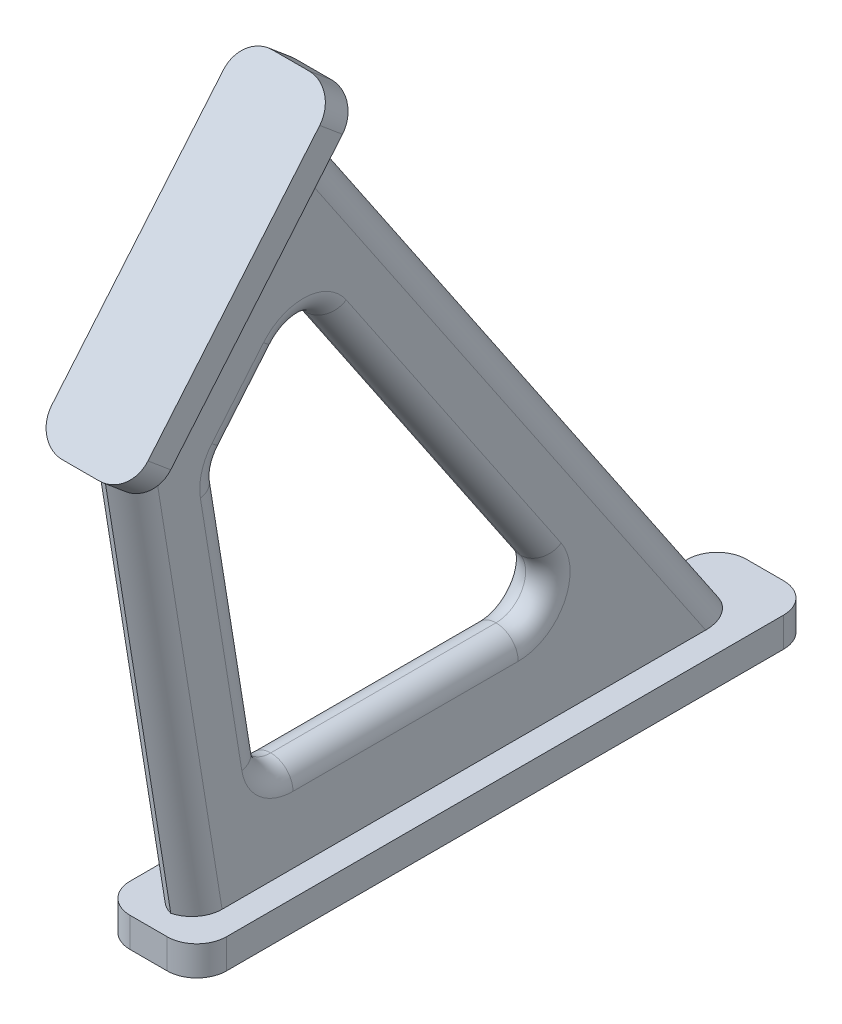
SolidWorks part; units mm, degrees
ref_plane "Front Plane" through (0, 0, 0) normal (0, 0, 1) x (1, 0, 0)
ref_plane "Top Plane" through (0, 0, 0) normal (0, 1, 0) x (1, 0, 0)
ref_plane "Right Plane" through (0, 0, 0) normal (1, 0, 0) x (0, 0, -1)
sketch "Sketch1" plane through (0, 0, 0) normal (1, 0, 0) x (0, 0, -1)
  line L0 (-43.305, 32.2596) -> (-38.1, 0)
  line L1 (-38.1, 0) -> (0, 0)
  line L2 (0, 0) -> (-31.3945, 46.4541)
  line L3 (-31.3945, 46.4541) -> (-43.305, 32.2596)
  line L4 (-30.1089, 47.9862) -> (-44.5716, 30.7502) construction
  point P2 (-44.5716, 30.7502)
  point P5 (-30.1089, 47.9862)
  point P7 (-43.305, 32.2596)
  point P8 (-31.3945, 46.4541)
  dimension "D1" = 38.1
  dimension "D2" = 18.5295
  dimension "D3" = 55.948
extrude "Boss-Extrude1" add sketch "Sketch1" along normal mid plane 3
sketch "Sketch2" plane through (0, 0, 0) normal (0, -1, 0) x (1, 0, 0)
  line L8 (-3.25, 39.85) -> (-3.25, -1.75)
  line L9 (-3.25, -1.75) -> (3.25, -1.75)
  line L10 (3.25, -1.75) -> (3.25, 39.85)
  line L11 (3.25, 39.85) -> (-3.25, 39.85)
  line L12 (-3.25, 39.85) -> (-3.25, -1.75)
  line L13 (-3.25, -1.75) -> (3.25, -1.75)
  line L14 (3.25, -1.75) -> (3.25, 39.85)
  line L15 (3.25, 39.85) -> (-3.25, 39.85)
  dimension "D1" = 1.75
extrude "Boss-Extrude2" add sketch "Sketch2" against normal blind 2
sketch "Sketch3" plane through (0, 34.6525, 41.2972) normal (0, 0.6428, 0.766) x (1, 0, 0)
  line L8 (-3.25, 17.1559) -> (-3.25, -4.8736)
  line L9 (-3.25, -4.8736) -> (3.25, -4.8736)
  line L10 (3.25, -4.8736) -> (3.25, 17.1559)
  line L11 (3.25, 17.1559) -> (-3.25, 17.1559)
  line L12 (-3.25, 17.1559) -> (-3.25, -4.8736)
  line L13 (-3.25, -4.8736) -> (3.25, -4.8736)
  line L14 (3.25, -4.8736) -> (3.25, 17.1559)
  line L15 (3.25, 17.1559) -> (-3.25, 17.1559)
  dimension "D1" = 1.75
extrude "Boss-Extrude3" add sketch "Sketch3" against normal blind 2
sketch "Sketch4" plane through (1.5, 0, 0) normal (1, 0, 0) x (0, 0, -1)
  line L8 (-33.3132, 8) -> (-12.6482, 8)
  line L9 (-36.5234, 27.8959) -> (-33.3132, 8)
  line L10 (-30.7468, 34.7802) -> (-36.5234, 27.8959)
  line L11 (-36.5234, 27.8959) -> (-33.3132, 8)
  line L12 (-33.3132, 8) -> (-12.6482, 8)
  line L14 (-30.7468, 34.7802) -> (-36.5234, 27.8959)
  line L16 (-12.6482, 8) -> (-30.7468, 34.7802)
  line L17 (-12.6482, 8) -> (-30.7468, 34.7802)
  dimension "D1" = 6
extrude "Cut-Extrude1" cut sketch "Sketch4" against normal through all both and the other way through all
fillet "Fillet1" radius 2 16 edges at (-1.5, 15.825, 40.6533) (-1.5, 23.3653, 15.7907) (1.5, 23.3653, 15.7907) (1.5, 15.825, 40.6533) (-3.25, 47.1519, 29.5036) (-3.25, 30.2763, 43.6639) (3.25, 47.1519, 29.5036) (3.25, 30.2763, 43.6639) (-3.25, 1, -1.75) (3.25, 1, -1.75) (-3.25, 1, 39.85) (3.25, 1, 39.85) (0, 34.7802, 30.7468) (0, 8, 12.6482) (0, 27.8959, 36.5234) (0, 8, 33.3132)
fillet "Fillet2" radius 1.5 16 edges at (1.5, 9.0619, 14.6475) (1.5, 21.8516, 22.0094) (1.5, 33.4607, 30.8153) (1.5, 30.6729, 34.1932) (1.5, 27.8429, 36.3312) (1.5, 18.337, 34.9811) (1.5, 8.4773, 32.9067) (-1.5, 9.0619, 14.6475) (-1.5, 21.8516, 22.0094) (-1.5, 33.4607, 30.8153) (-1.5, 30.6729, 34.1932) (-1.5, 27.8429, 36.3312) (-1.5, 18.337, 34.9811) (-1.5, 8.4773, 32.9067) (1.5, 8, 24.0119) (-1.5, 8, 24.0119)
